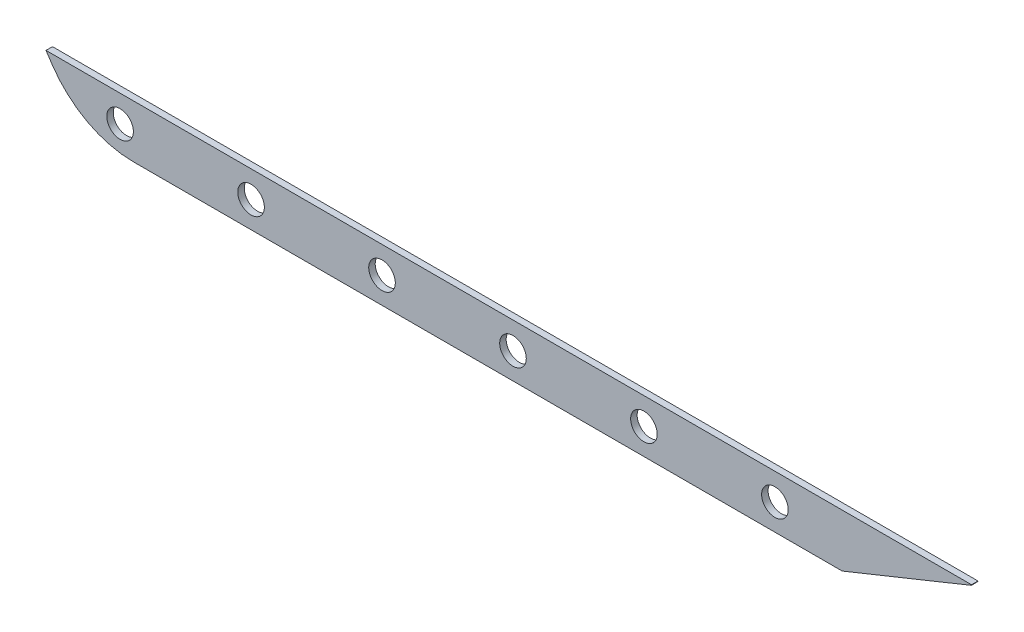
SolidWorks part; units mm, degrees
material "5052-H34"
ref_plane "Front Plane" through (0, 0, 0) normal (0, 0, 1) x (1, 0, 0)
ref_plane "Top Plane" through (0, 0, 0) normal (0, 1, 0) x (1, 0, 0)
ref_plane "Right Plane" through (0, 0, 0) normal (1, 0, 0) x (0, 0, -1)
sketch "Sketch1" plane through (0, 0, 0) normal (0, 0, 1) x (1, 0, 0)
  line L3 (428.1206, 28.9396) -> (0.5404, 28.9396)
  line L6 (-98.8794, 3.851) -> (-31.8794, -96.649)
  line L7 (428.1206, 28.9396) -> (403.1206, -71.149)
  line L9 (403.1206, -71.149) -> (366, -96.649)
  line L10 (-31.8794, -96.649) -> (366, -96.649)
  line L11 (0.5404, 28.9396) -> (-115.6052, 28.9396)
  line L12 (-98.8794, 3.851) -> (-115.6052, 28.9396)
  line L13 (-49.0861, -70.839) -> (403.198, -70.839)
  circle A0 centre (-12.8794, -83.899) radius 6.5
  circle A1 centre (51.1206, -83.899) radius 6.5
  circle A2 centre (115.1206, -83.899) radius 6.5
  circle A3 centre (179.1206, -83.899) radius 6.5
  circle A4 centre (243.1206, -83.899) radius 6.5
  circle A5 centre (307.1206, -83.899) radius 6.5
  point P0 (-48.8794, -71.149)
  point P2 (-31.8794, -96.649)
  point P8 (48, -83.899)
  point P9 (403.1206, -71.149)
  point P23 (-49.0861, -70.839)
  point P26 (403.198, -70.839)
  dimension "D2" = 64
  dimension "D4" = 64
  dimension "D1" = 25.5
  dimension "D3" = 75
  dimension "D5" = 25
  dimension "D6" = 96
  dimension "D7" = 527
  dimension "D8" = 180
  dimension "D9" = 64
  dimension "D10" = 64
  dimension "D11" = 64
  dimension "D12" = 123.69
  dimension "D13" = 12.75
  dimension "D14" = 25.81
  dimension "D15" = 25.81
extrude "Boss-Extrude1" add sketch "Sketch1" along normal blind 3.175 contours L3 L11 L12 L6 L10 L9 L7
extrude "Cut-Extrude1" cut sketch "Sketch1<4>" along normal through all contours A0 | A1 | A2 | A3 | A4 | A5 region at (-12.8794, -83.899, 0)
sketch "Sketch1<4>" plane through (0, 0, 0) normal (0, 0, 1) x (1, 0, 0) same geometry as "Sketch1"
sketch "Sketch2" plane through (0, 0, 0) normal (0, 0, -1) x (-1, 0, 0)
  circle A0 centre (-275.1206, -83.899) radius 6.5
  circle A2 centre (-233.5603, -132.5687) radius 6.5
  circle A3 centre (-192, -83.899) radius 6.5
  circle A4 centre (-128, -83.899) radius 6.5
  circle A5 centre (-64, -83.899) radius 6.5
  circle A6 centre (0, -83.899) radius 6.5
  dimension "D2" = 0
  dimension "D3" = 64
  dimension "D4" = 64
  dimension "D5" = 64
  dimension "D6" = 64
  dimension "D7" = 64
  dimension "D1" = 32
sketch "Sketch5" plane through (0, 0, 0) normal (0, 0, -1) x (-1, 0, 0)
  line L0 (48.8794, -71.149) -> (-14.2353, -96.649)
  line L1 (31.8794, -96.649) -> (-366, -96.649) construction
  line L2 (-14.2353, -96.649) -> (31.8794, -96.649)
  line L3 (31.8794, -96.649) -> (48.8794, -71.149)
  line L6 (-366, -96.649) -> (-403.1206, -71.149)
  line L7 (-403.1206, -71.149) -> (-352, -71.149)
  line L9 (-352, -71.149) -> (-326.5, -96.649)
  line L11 (-366, -96.649) -> (-326.5, -96.649)
  dimension "D1" = 22
  dimension "D2" = 45
extrude "Cut-Extrude2" [suppressed] cut sketch "Sketch5" against normal up to next
sketch "Sketch6" plane through (0, 0, 3.175) normal (0, 0, 1) x (1, 0, 0)
  line L0 (-48.8794, -71.149) -> (14.2353, -96.649)
  line L1 (-31.8794, -96.649) -> (366, -96.649) construction
  line L2 (14.2353, -96.649) -> (-31.8794, -96.649)
  line L3 (-31.8794, -96.649) -> (-48.8794, -71.149)
  dimension "D1" = 158
fillet "Fillet1" radius 48 1 edges at (-31.8794, -96.649, 1.5875)
sketch "Sketch7" plane through (0, 0, 3.175) normal (0, 0, 1) x (1, 0, 0)
  line L0 (403.1206, -71.149) -> (340.0059, -96.649)
  line L1 (-31.8794, -96.649) -> (366, -96.649) construction
  line L2 (340.0059, -96.649) -> (366, -96.649)
  line L3 (366, -96.649) -> (403.1206, -71.149)
  dimension "D1" = 22
extrude "Cut-Extrude3" cut sketch "Sketch7" against normal blind 10
sketch "Sketch9" plane through (0, 0, 0) normal (0, 0, -1) x (-1, 0, 0)
  line L0 (-403.1206, -71.149) -> (48.8794, -71.149)
  line L1 (48.8794, -71.149) -> (48.8794, -114.9143)
  line L2 (48.8794, -114.9143) -> (-403.1206, -114.9143)
  line L3 (-403.1206, -114.9143) -> (-403.1206, -71.149)
extrude "Cut-Extrude4" [suppressed] cut sketch "Sketch9" against normal blind 10
sketch "Sketch10" plane through (0, 0, 3.175) normal (0, 0, 1) x (1, 0, 0)
  line L0 (-49.0861, -70.839) -> (403.198, -70.839) construction
  line L1 (-49.0861, -70.839) -> (403.198, -70.839)
  line L2 (-49.0861, -70.839) -> (-115.6052, 28.9396)
  line L3 (-115.6052, 28.9396) -> (428.1206, 28.9396)
  line L4 (428.1206, 28.9396) -> (403.198, -70.839)
extrude "Cut-Extrude5" cut sketch "Sketch10" against normal blind 10
